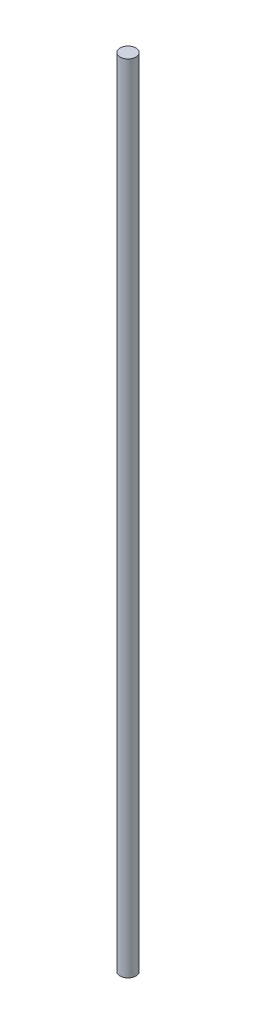
SolidWorks part; units mm, degrees
material "AISI 316 Annealed Stainless Steel Bar (SS)"
ref_plane "Front Plane" through (0, 0, 0) normal (0, 0, 1) x (1, 0, 0)
ref_plane "Top Plane" through (0, 0, 0) normal (0, 1, 0) x (1, 0, 0)
ref_plane "Right Plane" through (0, 0, 0) normal (1, 0, 0) x (0, 0, -1)
sketch "Sketch1" plane through (0, 0, 0) normal (0, 1, 0) x (1, 0, 0)
  circle A0 centre (0, 0) radius 4
  dimension "D1" = 8
extrude "Boss-Extrude1" add sketch "Sketch1" against normal blind 400
equation "\"rod_diameter\"= 8"
equation "\"rod_hole_thickness\"= 4"
equation "\"rod_radius\"= \"rod_diameter\" / 2"
equation "\"platter_diameter\"= 320"
equation "\"platter_radius\"= \"platter_diameter\" / 2"
equation "\"extruder_mount_hole_spacing\"= 75"
equation "\"arm_rod_spacing\"= 40"
equation "\"top_frame_rod_spacing\"= \"arm_rod_spacing\" + 40"
equation "\"motor_level_rod_spacing\"= 15"
equation "\"linear_bearing_diameter\"= 15"
equation "\"z_rod_spacing\"= 75"
equation "\"platter_rod_spacing\"= 50"
equation "\"rod_nut_thickness\"= 6.5"
equation "\"rod_nut_inscribed_diameter\"= 13"
equation "\"z_height\"= 400"
equation "\"D1@Sketch1\"= \"rod_diameter\""
equation "\"D1@Boss-Extrude1\"= \"z_height\""
